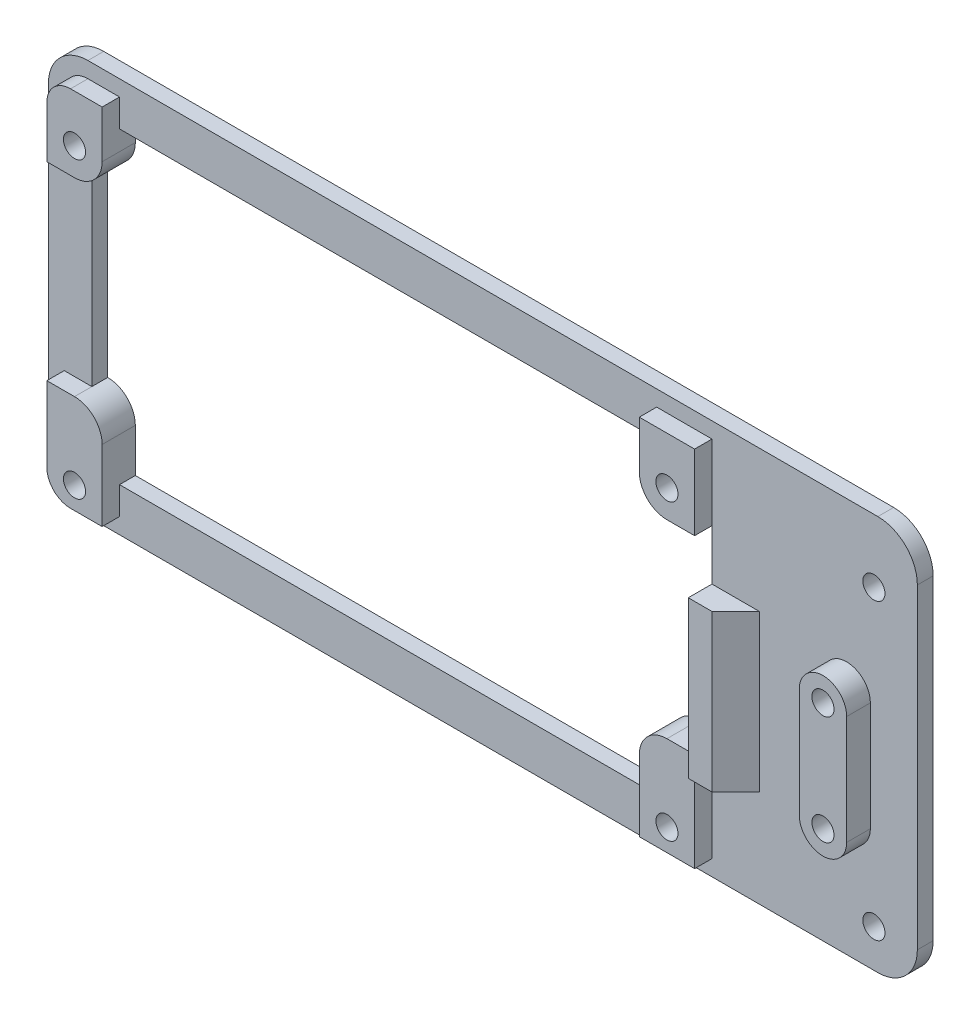
SolidWorks part; units mm, degrees
material "PET"
ref_plane "Přední rovina" through (0, 0, 0) normal (0, 0, 1) x (1, 0, 0)
ref_plane "Horní rovina" through (0, 0, 0) normal (0, 1, 0) x (1, 0, 0)
ref_plane "Pravá rovina" through (0, 0, 0) normal (1, 0, 0) x (0, 0, -1)
sketch "Skica1" plane through (0, 0, 0) normal (0, 0, 1) x (1, 0, 0)
  line L1 (0, 0) -> (110, 0)
  line L2 (0, 0) -> (0, 50)
  line L3 (0, 50) -> (110, 50)
  line L4 (110, 0) -> (110, 50)
  line L5 (0, 0) -> (110, 50) construction
  line L6 (0, 50) -> (110, 0) construction
  line L7 (2, 48) -> (84, 48)
  line L8 (2, 48) -> (2, 2)
  line L9 (2, 2) -> (84, 2)
  line L10 (84, 48) -> (84, 2)
  line L11 (2, 48) -> (84, 2) construction
  line L12 (2, 2) -> (84, 48) construction
  point P4 (55, 25)
  point P10 (43, 25)
  dimension "D1" = 110
  dimension "D2" = 50
  dimension "D3" = 2
  dimension "D4" = 2
  dimension "D5" = 2
  dimension "D6" = 82
extrude "Přidat vysunutím1" add sketch "Skica1" along normal blind 2
sketch "Skica2" plane through (0, 0, 0) normal (0, 0, -1) x (-1, 0, 0)
  line L0 (-84, 25) -> (-2, 25) construction
  line L1 (-84, 2) -> (-84, 48) construction
  line L2 (-2, 48) -> (-2, 2) construction
  line L3 (-110, 50) -> (0, 50) construction
  line L4 (-5.5, 4.8) -> (-80.5, 4.8) construction
  line L5 (-5.5, 4.8) -> (-5.5, 42) construction
  line L6 (-5.5, 42) -> (-80.5, 42) construction
  line L7 (-80.5, 4.8) -> (-80.5, 42) construction
  line L8 (-5.5, 4.8) -> (-80.5, 42) construction
  line L9 (-5.5, 42) -> (-80.5, 4.8) construction
  line L10 (-80.5, 11) -> (-5.5, 11) construction
  line L11 (-77, 42) -> (-77, 48)
  line L12 (-84, 48) -> (-2, 48) construction
  line L13 (-77, 48) -> (-84, 48)
  line L14 (-80.5, 38.5) -> (-84, 38.5)
  line L15 (-84, 38.5) -> (-84, 48)
  line L16 (-9, 42) -> (-9, 48)
  line L17 (-9, 48) -> (-2, 48)
  line L18 (-2, 48) -> (-2, 38.5)
  line L19 (-2, 38.5) -> (-5.5, 38.5)
  line L20 (-80.5, 14.5) -> (-84, 14.5)
  line L21 (-77, 11) -> (-77, 2)
  line L22 (-2, 2) -> (-84, 2) construction
  line L23 (-77, 2) -> (-84, 2)
  line L24 (-84, 2) -> (-84, 14.5)
  line L25 (-5.5, 14.5) -> (-2, 14.5)
  line L26 (-2, 14.5) -> (-2, 2)
  line L27 (-2, 2) -> (-9, 2)
  line L28 (-9, 2) -> (-9, 11)
  circle A0 centre (-80.5, 42) radius 1.4
  circle A1 centre (-5.5, 42) radius 1.4
  circle A3 centre (-80.5, 4.8) radius 1.4
  circle A4 centre (-5.5, 4.8) radius 1.4
  arc A5 (-80.5, 38.5) -> (-77, 42) centre (-80.5, 42) ccw
  arc A6 (-9, 42) -> (-5.5, 38.5) centre (-5.5, 42) ccw
  arc A7 (-77, 11) -> (-80.5, 14.5) centre (-80.5, 11) ccw
  arc A8 (-5.5, 14.5) -> (-9, 11) centre (-5.5, 11) ccw
  point P6 (-43, 23.4)
  dimension "D4" = 2.8
  dimension "D5" = 2.8
  dimension "D6" = 31
  dimension "D7" = 2.8
  dimension "D8" = 2.8
  dimension "D9" = 7
  dimension "D10" = 7
  dimension "D1" = 37.2
  dimension "D2" = 75
  dimension "D3" = 8
extrude "Přidat vysunutím2" add sketch "Skica2" against normal up to surface (2 mm away) up to face at (55, 25, 2)
fillet "Zaoblit1" radius 5 4 edges at (110, 50, 1) (110, 0, 1) (0, 0, 1) (0, 50, 1)
sketch "Skica3" plane through (0, 0, 2) normal (0, 0, 1) x (1, 0, 0)
  line L0 (5, 0) -> (105, 0) construction
  line L9 (110, 5) -> (110, 45) construction
  line L10 (101.05, 29.1) -> (101.05, 15.3) construction
  line L11 (85, 36.1) -> (103.6, 36.1) construction
  line L12 (85, 36.1) -> (85, 9.8) construction
  line L13 (85, 9.8) -> (103.6, 9.8) construction
  line L14 (103.6, 36.1) -> (103.6, 9.8) construction
  line L15 (85, 36.1) -> (103.6, 9.8) construction
  line L16 (85, 9.8) -> (103.6, 36.1) construction
  circle A0 centre (93, 20) radius 5 construction
  circle A1 centre (101.05, 29.1) radius 1.4
  circle A2 centre (101.05, 15.3) radius 1.4
  point P18 (94.3, 22.95)
  dimension "D1" = 17
  dimension "D3" = 10
  dimension "D7" = 2.8
  dimension "D8" = 2.8
  dimension "D2" = 18.6
  dimension "D4" = 26.3
  dimension "D5" = 8
  dimension "D6" = 10.2
  dimension "D9" = 13.8
  dimension "D10" = 5.5
  dimension "D11" = 2.55
  dimension "D12" = 20
extrude "Odebrat vysunutím1" cut sketch "Skica3" against normal up to surface (2 mm away) up to face at (43, 26.125, 0)
sketch "Skica4" plane through (0, 0, 2) normal (0, 0, 1) x (1, 0, 0)
  line L0 (101.05, 29.1) -> (101.05, 15.3) construction
  line L1 (104.05, 29.1) -> (104.05, 15.3)
  line L2 (98.05, 29.1) -> (98.05, 15.3)
  circle A0 centre (101.05, 15.3) radius 1.4 construction
  circle A1 centre (101.05, 29.1) radius 1.4 construction
  circle A2 centre (101.05, 15.3) radius 1.4
  circle A3 centre (101.05, 29.1) radius 1.4
  arc A4 (104.05, 29.1) -> (98.05, 29.1) centre (101.05, 29.1) ccw
  arc A5 (98.05, 15.3) -> (104.05, 15.3) centre (101.05, 15.3) ccw
  point P6 (101.05, 22.2)
  dimension "D1" = 6
extrude "Přidat vysunutím3" add sketch "Skica4" along normal blind 3
sketch "Skica5" plane through (0, 0, 2) normal (0, 0, 1) x (1, 0, 0)
  line L15 (2, 38.5) -> (5.5, 38.5) construction
  line L16 (9, 42) -> (9, 48) construction
  line L17 (77, 48) -> (9, 48) construction
  line L18 (77, 48) -> (77, 42) construction
  line L19 (5.5, 14.5) -> (2, 14.5) construction
  line L20 (9, 2) -> (9, 11) construction
  line L21 (9, 2) -> (77, 2) construction
  line L22 (77, 11) -> (77, 2) construction
  line L23 (84, 14.5) -> (80.5, 14.5) construction
  line L24 (80.5, 38.5) -> (84, 38.5) construction
  line L25 (2, 38.5) -> (5.5, 38.5)
  line L27 (5.5, 14.5) -> (2, 14.5)
  line L28 (9, 2) -> (9, 11)
  line L29 (9, 2) -> (77, 2)
  line L30 (77, 11) -> (77, 2)
  line L31 (84, 14.5) -> (80.5, 14.5)
  line L33 (80.5, 38.5) -> (84, 38.5)
  line L34 (77, 48) -> (77, 42)
  line L35 (77, 48) -> (9, 48)
  line L36 (9, 42) -> (9, 48)
  line L37 (2, 45) -> (2, 5)
  line L38 (5, 2) -> (84, 2)
  line L40 (84, 48) -> (5, 48)
  line L45 (84, 38.5) -> (84, 48)
  line L46 (84, 14.5) -> (84, 2)
  arc A12 (5.5, 38.5) -> (9, 42) centre (5.5, 42) ccw construction
  arc A13 (77, 42) -> (80.5, 38.5) centre (80.5, 42) ccw construction
  circle A14 centre (5.5, 4.8) radius 1.4 construction
  circle A15 centre (80.5, 4.8) radius 1.4 construction
  circle A16 centre (80.5, 42) radius 1.4 construction
  circle A17 centre (5.5, 42) radius 1.4 construction
  arc A18 (9, 11) -> (5.5, 14.5) centre (5.5, 11) ccw construction
  arc A19 (80.5, 14.5) -> (77, 11) centre (80.5, 11) ccw construction
  circle A20 centre (5.5, 4.8) radius 1.4
  circle A21 centre (80.5, 4.8) radius 1.4
  circle A22 centre (80.5, 42) radius 1.4
  circle A23 centre (5.5, 42) radius 1.4
  arc A24 (5.5, 38.5) -> (9, 42) centre (5.5, 42) ccw
  arc A25 (9, 11) -> (5.5, 14.5) centre (5.5, 11) ccw
  arc A26 (80.5, 14.5) -> (77, 11) centre (80.5, 11) ccw
  arc A27 (77, 42) -> (80.5, 38.5) centre (80.5, 42) ccw
  arc A28 (5, 48) -> (2, 45) centre (5, 45) ccw
  arc A29 (2, 5) -> (5, 2) centre (5, 5) ccw
  point P46 (87, 2)
  point P47 (87, 48)
  circle M17 centre (5.5, 4.8) radius 1.4
  circle M18 centre (80.5, 4.8) radius 1.4
  circle M19 centre (80.5, 42) radius 1.4
  circle M20 centre (5.5, 42) radius 1.4
  line M30 (2, 38.5) -> (5.5, 38.5)
  arc M31 (5.5, 38.5) -> (9, 42) centre (5.5, 42) ccw
  line M32 (9, 42) -> (9, 48)
  line M34 (77, 48) -> (77, 42)
  arc M35 (77, 42) -> (80.5, 38.5) centre (80.5, 42) ccw
  line M36 (80.5, 38.5) -> (84, 38.5)
  line M38 (84, 14.5) -> (80.5, 14.5)
  arc M39 (80.5, 14.5) -> (77, 11) centre (80.5, 11) ccw
  line M40 (77, 11) -> (77, 2)
  line M42 (9, 2) -> (9, 11)
  arc M43 (9, 11) -> (5.5, 14.5) centre (5.5, 11) ccw
  line M44 (5.5, 14.5) -> (2, 14.5)
extrude "Přidat vysunutím5" add sketch "Skica5" along normal blind 2.2 contours L40 A28 L37 M30 M31 M32 M20 | L37 A29 L38 M42 M43 M44 M17 | L45 L40 M36 M34 M35 M19 | L46 L38 M38 M39 M40 M18 region at (5.4699, 43.4337, 2) region at (80.6238, 43.5641, 2) region at (80.5908, 8.3373, 2) region at (5.4781, 8.4798, 2)
sketch "Skica6" plane through (0, 0, 0) normal (0, 0, -1) x (-1, 0, 0)
  line L1 (-80.5, 42) -> (-104.5, 42) construction
  line L2 (-80.5, 42) -> (-80.5, 4.8) construction
  line L3 (-80.5, 4.8) -> (-104.5, 4.8) construction
  line L4 (-104.5, 42) -> (-104.5, 4.8) construction
  line L5 (-80.5, 42) -> (-104.5, 4.8) construction
  line L6 (-80.5, 4.8) -> (-104.5, 42) construction
  line L7 (-110, 5) -> (-110, 45) construction
  circle A0 centre (-104.5, 42) radius 1.4
  circle A1 centre (-104.5, 4.8) radius 1.4
  point P4 (-92.5, 23.4)
  dimension "D1" = 2.8
  dimension "D2" = 2.8
  dimension "D3" = 5.5
extrude "Odebrat vysunutím2" cut sketch "Skica6" against normal up to surface (2 mm away) up to face at (101.05, 22.2, 2)
sketch "Skica8" plane through (0, 0, 2) normal (0, 0, 1) x (1, 0, 0)
  line L0 (84, 14.5) -> (84, 2) construction
  line L1 (84, 12.3) -> (87, 12.3)
  line L2 (84, 12.3) -> (84, 32.1)
  line L3 (84, 32.1) -> (87, 32.1)
  line L4 (87, 12.3) -> (87, 32.1)
  line L5 (84, 12.3) -> (87, 32.1) construction
  line L6 (84, 32.1) -> (87, 12.3) construction
  arc A0 (104.05, 29.1) -> (98.05, 29.1) centre (101.05, 29.1) ccw construction
  arc A1 (98.05, 15.3) -> (104.05, 15.3) centre (101.05, 15.3) ccw construction
  point P4 (85.5, 22.2)
  dimension "D1" = 3
extrude "Přidat vysunutím6" add sketch "Skica8" along normal up to surface (3 mm away) up to face at (102.45, 15.3, 5)
chamfer "Zkosení1" distance 3 angle 45 1 edges at (87, 22.2, 2)
sketch "Skica9" plane through (0, 0, 0) normal (0, 0, -1) x (-1, 0, 0)
  line L0 (-9, 11) -> (-9, 2) construction
  line L1 (-77, 2) -> (-9, 2)
  line L2 (-77, 2) -> (-77, 5.5)
  line L3 (-77, 5.5) -> (-9, 5.5)
  line L4 (-9, 2) -> (-9, 5.5)
  line L5 (-77, 2) -> (-9, 5.5) construction
  line L6 (-77, 5.5) -> (-9, 2) construction
  line L7 (-9, 48) -> (-9, 42) construction
  line L8 (-77, 48) -> (-9, 48)
  line L9 (-77, 48) -> (-77, 44.5)
  line L10 (-77, 44.5) -> (-9, 44.5)
  line L11 (-9, 48) -> (-9, 44.5)
  line L12 (-77, 48) -> (-9, 44.5) construction
  line L13 (-77, 44.5) -> (-9, 48) construction
  line L14 (-2, 14.5) -> (-5.5, 14.5) construction
  line L15 (-2, 38.5) -> (-5.5, 38.5)
  line L16 (-2, 38.5) -> (-2, 14.5)
  line L17 (-2, 14.5) -> (-5.5, 14.5)
  line L18 (-5.5, 38.5) -> (-5.5, 14.5)
  line L19 (-2, 38.5) -> (-5.5, 14.5) construction
  line L20 (-2, 14.5) -> (-5.5, 38.5) construction
  point P4 (-43, 3.75)
  point P12 (-43, 46.25)
  point P20 (-3.75, 26.5)
  dimension "D1" = 3.5
  dimension "D2" = 3.5
  dimension "D3" = 3.5
extrude "Přidat vysunutím7" add sketch "Skica9" against normal up to surface (2 mm away) up to face at (55, 25, 2)
